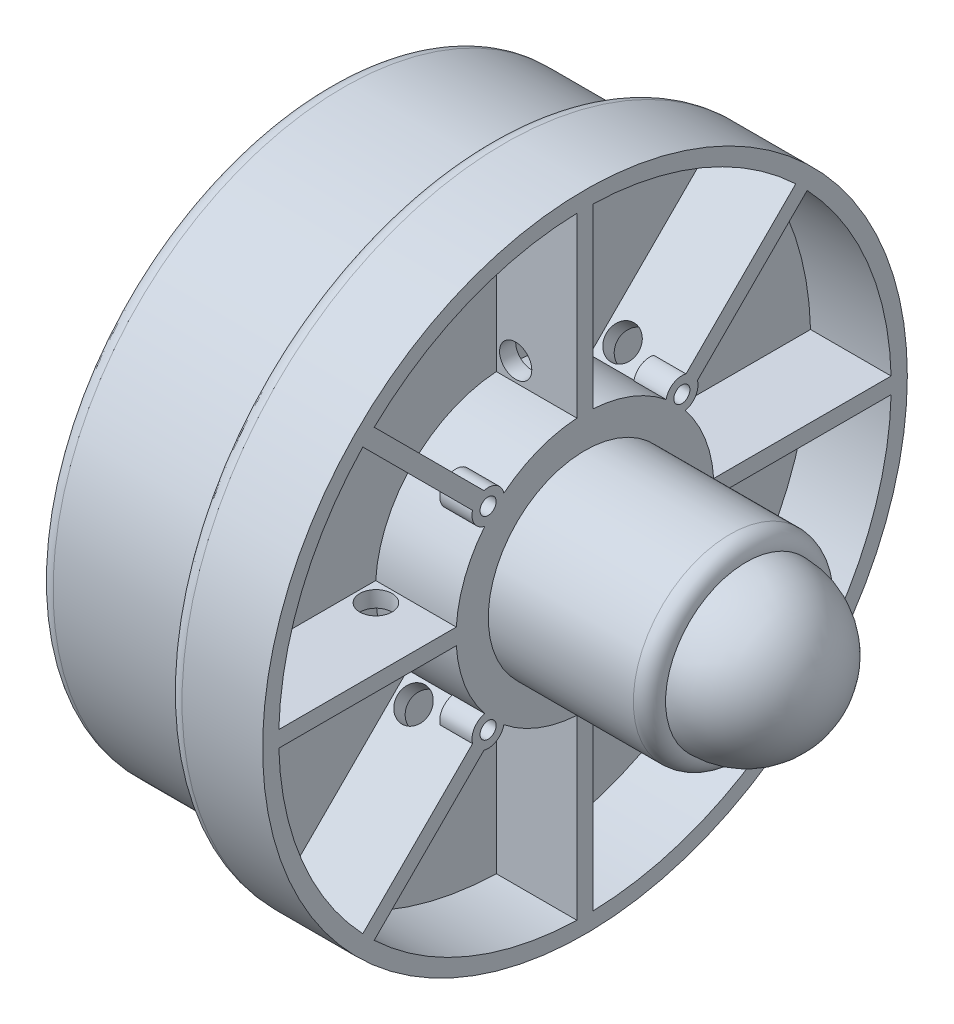
SolidWorks part; units mm, degrees
ref_plane "Front Plane" through (0, 0, 0) normal (0, 0, 1) x (1, 0, 0)
ref_plane "Top Plane" through (0, 0, 0) normal (0, 1, 0) x (1, 0, 0)
ref_plane "Right Plane" through (0, 0, 0) normal (1, 0, 0) x (0, 0, -1)
sketch "Sketch1" plane through (0, 0, 0) normal (1, 0, 0) x (0, 0, -1)
  circle A0 centre (0, 0) radius 19.05
  circle A1 centre (0, 0) radius 22.86
  dimension "D1" = 38.1
  dimension "D2" = 45.72
extrude "Boss-Extrude1" add sketch "Sketch1" along normal blind 12.7
sketch "Sketch2" plane through (12.7, 0, 0) normal (1, 0, 0) x (0, 0, -1)
  circle A0 centre (0, 0) radius 25.4
  dimension "D1" = 50.8
extrude "Boss-Extrude2" add sketch "Sketch2" along normal blind 1.27
fillet "Fillet1" radius 1.27 1 edges at (0, 0, -22.86)
sketch "Sketch3" plane through (13.97, 0, 0) normal (1, 0, 0) x (0, 0, -1)
  circle A0 centre (0, 0) radius 25.4
  circle A1 centre (0, 0) radius 24.13
  circle A2 centre (0, 0) radius 25.4 construction
  circle A3 centre (0, 0) radius 10.16
  circle M1 centre (0, 0) radius 25.4
  dimension "D1" = 1.27
  dimension "D2" = 20.32
extrude "Boss-Extrude3" add sketch "Sketch3" along normal blind 6.35 contours A1 M1 | A3 region at (13.97, 0, 24.6816) region at (13.97, 0, 0)
sketch "Sketch4" plane through (20.32, 0, 0) normal (1, 0, 0) x (0, 0, -1)
  circle A0 centre (0, 0) radius 7.62
  dimension "D1" = 15.24
extrude "Boss-Extrude4" add sketch "Sketch4" along normal blind 12.7
sketch "Sketch5" plane through (13.97, 0, 0) normal (1, 0, 0) x (0, 0, -1)
  line L0 (0, 0) -> (0, 25.4) construction
  line L1 (0.635, 24.765) -> (-0.635, 24.765)
  line L2 (-0.635, 24.765) -> (-0.635, 7.5935)
  line L3 (-0.635, 7.5935) -> (0.635, 7.5935)
  line L4 (0.635, 7.5935) -> (0.635, 24.765)
  line L5 (5.8184, 4.9204) -> (17.9605, 17.0625)
  line L6 (17.0625, 17.9605) -> (4.9204, 5.8184)
  line L7 (4.9204, 5.8184) -> (5.8184, 4.9204)
  line L8 (17.9605, 17.0625) -> (17.0625, 17.9605)
  line L9 (0, 0) -> (17.9605, 17.9605) construction
  line L10 (7.5935, -0.635) -> (24.765, -0.635)
  line L11 (24.765, 0.635) -> (7.5935, 0.635)
  line L12 (7.5935, 0.635) -> (7.5935, -0.635)
  line L13 (24.765, -0.635) -> (24.765, 0.635)
  line L14 (0, 0) -> (25.4, 0) construction
  line L15 (4.9204, -5.8184) -> (17.0625, -17.9605)
  line L16 (17.9605, -17.0625) -> (5.8184, -4.9204)
  line L17 (5.8184, -4.9204) -> (4.9204, -5.8184)
  line L18 (17.0625, -17.9605) -> (17.9605, -17.0625)
  line L19 (0, 0) -> (17.9605, -17.9605) construction
  line L20 (-0.635, -7.5935) -> (-0.635, -24.765)
  line L21 (0.635, -24.765) -> (0.635, -7.5935)
  line L22 (0.635, -7.5935) -> (-0.635, -7.5935)
  line L23 (-0.635, -24.765) -> (0.635, -24.765)
  line L24 (0, 0) -> (0, -25.4) construction
  line L25 (-5.8184, -4.9204) -> (-17.9605, -17.0625)
  line L26 (-17.0625, -17.9605) -> (-4.9204, -5.8184)
  line L27 (-4.9204, -5.8184) -> (-5.8184, -4.9204)
  line L28 (-17.9605, -17.0625) -> (-17.0625, -17.9605)
  line L29 (0, 0) -> (-17.9605, -17.9605) construction
  line L30 (-7.5935, 0.635) -> (-24.765, 0.635)
  line L31 (-24.765, -0.635) -> (-7.5935, -0.635)
  line L32 (-7.5935, -0.635) -> (-7.5935, 0.635)
  line L33 (-24.765, 0.635) -> (-24.765, -0.635)
  line L34 (0, 0) -> (-25.4, 0) construction
  line L35 (-4.9204, 5.8184) -> (-17.0625, 17.9605)
  line L36 (-17.9605, 17.0625) -> (-5.8184, 4.9204)
  line L37 (-5.8184, 4.9204) -> (-4.9204, 5.8184)
  line L38 (-17.0625, 17.9605) -> (-17.9605, 17.0625)
  line L39 (0, 0) -> (-17.9605, 17.9605) construction
  circle A0 centre (0, 0) radius 25.4 construction
  circle A2 centre (0, 0) radius 7.62 construction
  circle A3 centre (0, 0) radius 7.62 construction
  point P9 (0, 24.765)
  point P53 (0, 0)
  dimension "D1" = 1.27
  dimension "D3" = 0.635
  dimension "D2" = 8
extrude "Boss-Extrude8" add sketch "Sketch5" along normal blind 6.35
sketch "Sketch7" plane through (0, 0, 0) normal (0, 0, 1) x (1, 0, 0)
  line L0 (13.97, 10.1401) -> (20.32, 10.1401) construction
  line L1 (13.97, 24.1216) -> (13.97, 10.1401) construction
  line L2 (0, 0) -> (33.02, 0) construction
  line L3 (33.02, -7.62) -> (33.02, 7.62) construction
  circle A0 centre (15.494, 11.6641) radius 1.27
  dimension "D1" = 2.54
  dimension "D2" = 1.524
  dimension "D3" = 1.524
revolve "Cut-Revolve1" cut sketch "Sketch7" angle 360 about L2
sketch "Sketch8" plane through (20.32, 0, 0) normal (1, 0, 0) x (0, 0, -1)
  line L0 (-7.6332, 7.6332) -> (0, 0) construction
  line L1 (0, 0) -> (0, 10.795) construction
  circle A0 centre (0, 0) radius 10.795 construction
  circle A1 centre (-7.6332, 7.6332) radius 1.27
  circle A2 centre (7.6332, 7.6332) radius 1.27
  circle A3 centre (7.6332, -7.6332) radius 1.27
  circle A4 centre (-7.6332, -7.6332) radius 1.27
  point P15 (0, 0)
  dimension "D1" = 21.59
  dimension "D2" = 2.54
  dimension "D3" = 45
  dimension "D4" = 4
extrude "Boss-Extrude9" add sketch "Sketch8" against normal blind 2.54
sketch "Sketch9" plane through (20.32, 0, 0) normal (1, 0, 0) x (0, 0, -1)
  circle A0 centre (-7.6332, 7.6332) radius 0.635
  arc A1 (-6.3911, 7.898) -> (-7.9619, 8.8599) centre (-7.6332, 7.6332) ccw construction
  dimension "D1" = 1.27
extrude "Cut-Extrude2" cut sketch "Sketch9" against normal blind 2.286
pattern_circular "CirPattern1" count 4 over 360 about axis through (33.02, 0, 0) along (1, 0, 0) of "Cut-Extrude2"
fillet "Fillet2" radius 1.27 1 edges at (33.02, 0, -7.62)
sketch "Sketch10" plane through (33.02, 0, 0) normal (1, 0, 0) x (0, 0, -1)
  circle A0 centre (0, 0) radius 6.35
  circle A1 centre (0, 0) radius 6.35 construction
extrude "Boss-Extrude10" add sketch "Sketch10" along normal blind 6.35
fillet "Fillet3" radius 6.35 1 edges at (39.37, 0, -6.35)
sketch "Sketch11" plane through (20.32, 0, 0) normal (1, 0, 0) x (0, 0, -1)
  circle A0 centre (0, 0) radius 10.795 construction
  dimension "D1" = 21.59
fillet "Fillet4" radius 1.27 1 edges at (12.7, 0, -25.4)
